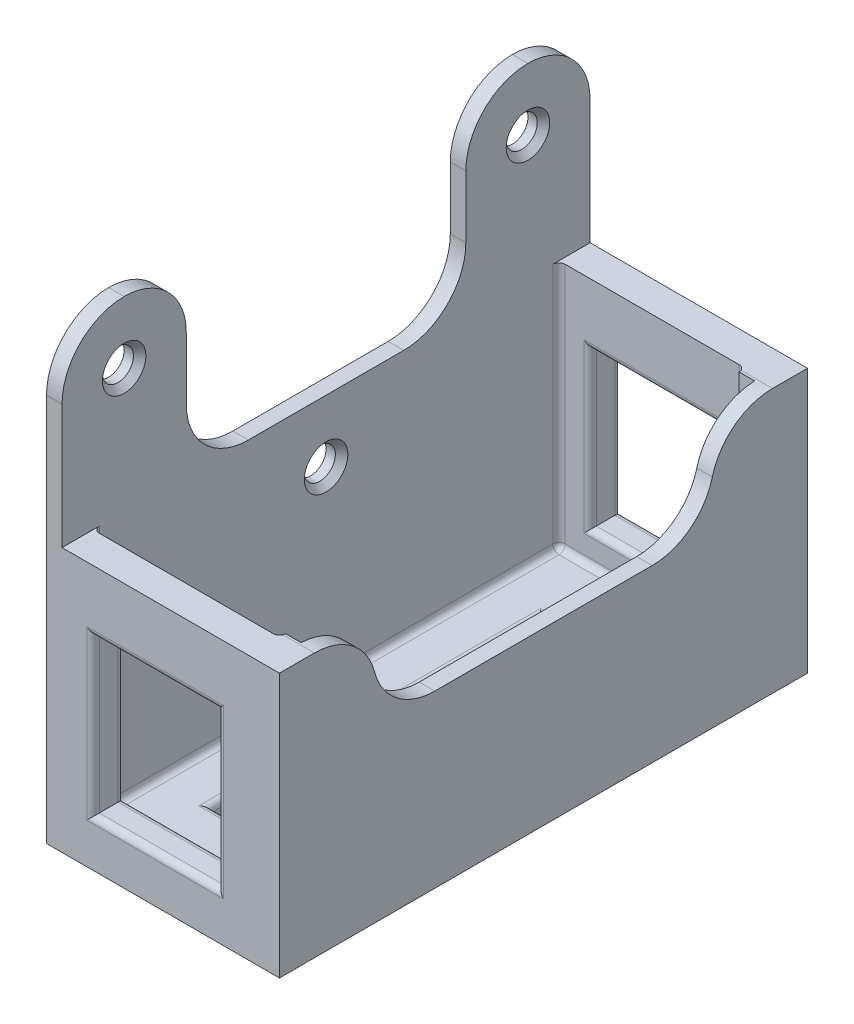
SolidWorks part; units mm, degrees
ref_plane "Front Plane" through (0, 0, 0) normal (0, 0, 1) x (1, 0, 0)
ref_plane "Top Plane" through (0, 0, 0) normal (0, 1, 0) x (1, 0, 0)
ref_plane "Right Plane" through (0, 0, 0) normal (1, 0, 0) x (0, 0, -1)
sketch "Sketch1" plane through (0, 0, 0) normal (0, 1, 0) x (1, 0, 0)
  line L1 (-31.1538, -30.9615) -> (8.8462, -30.9615)
  line L2 (-31.1538, -30.9615) -> (-31.1538, 54.0385)
  line L3 (-31.1538, 54.0385) -> (8.8462, 54.0385)
  line L4 (8.8462, -30.9615) -> (8.8462, 54.0385)
  dimension "D1" = 85
  dimension "D2" = 40
extrude "Boss-Extrude1" add sketch "Sketch1" along normal blind 75
sketch "Sketch3" plane through (0, 75, 0) normal (0, 1, 0) x (1, 0, 0)
  line L0 (-26.1538, -25.9615) -> (-26.1538, 49.0385)
  line L1 (-31.1538, -30.9615) -> (8.8462, -30.9615)
  line L2 (-31.1538, -30.9615) -> (-31.1538, 54.0385)
  line L3 (-31.1538, 54.0385) -> (8.8462, 54.0385)
  line L4 (8.8462, -30.9615) -> (8.8462, 54.0385)
  line L5 (-26.1538, 49.0385) -> (3.8462, 49.0385)
  line L6 (3.8462, -25.9615) -> (3.8462, 49.0385)
  line L7 (-26.1538, -25.9615) -> (3.8462, -25.9615)
  dimension "D1" = 5
extrude "Cut-Extrude2" cut sketch "Sketch3" against normal blind 70 flip side to cut
sketch "Sketch4" plane through (0, 75, 0) normal (0, 1, 0) x (1, 0, 0)
  line L0 (-31.1538, -30.9615) -> (8.8462, -30.9615) construction
  line L1 (-26.1538, -30.9615) -> (8.8462, -30.9615)
  line L2 (-26.1538, -30.9615) -> (-26.1538, 54.0385)
  line L3 (-26.1538, 54.0385) -> (8.8462, 54.0385)
  line L4 (8.8462, -30.9615) -> (8.8462, 54.0385)
extrude "Cut-Extrude3" cut sketch "Sketch4" against normal blind 30
fillet "Fillet1" radius 10 2 edges at (-28.6538, 75, -54.0385) (-28.6538, 75, 30.9615)
sketch "Sketch5" plane through (-26.1538, 0, 0) normal (1, 0, 0) x (0, 0, -1)
  circle A0 centre (-20.9615, 65) radius 2.5
  circle A1 centre (44.0385, 65) radius 2.5
extrude "Cut-Extrude4" cut sketch "Sketch5" against normal blind 30
chamfer "Chamfer1" distance 1 angle 45 2 edges at (-26.1538, 65, 18.4615) (-26.1538, 65, -46.5385)
sketch "Sketch6" plane through (8.8462, 0, 0) normal (1, 0, 0) x (0, 0, -1)
  line L0 (-30.9615, 45) -> (54.0385, 45) construction
  line L1 (-15.9615, 45) -> (39.0385, 45)
  line L2 (-15.9615, 45) -> (-15.9615, 40)
  line L3 (-5.9615, 30) -> (29.0385, 30)
  line L4 (39.0385, 45) -> (39.0385, 40)
  line L5 (-30.9615, 45) -> (-30.9615, 0) construction
  line L6 (54.0385, 45) -> (54.0385, 0) construction
  arc A0 (39.0385, 40) -> (29.0385, 30) centre (29.0385, 40) cw
  arc A1 (-5.9615, 30) -> (-15.9615, 40) centre (-5.9615, 40) cw
  point P14 (-15.9615, 30)
  dimension "D4" = 10
  dimension "D1" = 15
  dimension "D2" = 15
  dimension "D3" = 15
extrude "Cut-Extrude5" cut sketch "Sketch6" against normal blind 30
fillet "Fillet2" radius 1 8 edges at (3.8462, 25, -49.0385) (3.8462, 25, 25.9615) (3.8462, 5, -11.5385) (-11.1538, 5, -49.0385) (-26.1538, 25, -49.0385) (-26.1538, 25, 25.9615) (-11.1538, 5, 25.9615) (-26.1538, 5, -11.5385)
fillet "Fillet3" radius 10 2 edges at (6.3462, 45, 15.9615) (6.3462, 45, -39.0385)
sketch "Sketch7" plane through (0, 5, 0) normal (0, 1, 0) x (1, 0, 0)
  line L0 (2.8462, 48.0385) -> (-25.1538, 48.0385) construction
  line L1 (-18.1538, -14.9615) -> (-4.1538, -14.9615)
  line L2 (-18.1538, -14.9615) -> (-18.1538, 38.0385)
  line L3 (-18.1538, 38.0385) -> (-4.1538, 38.0385)
  line L4 (-4.1538, -14.9615) -> (-4.1538, 38.0385)
  line L5 (-25.1538, -24.9615) -> (2.8462, -24.9615) construction
  line L6 (-25.1538, 48.0385) -> (-25.1538, -24.9615) construction
  line L7 (2.8462, -24.9615) -> (2.8462, 48.0385) construction
  dimension "D1" = 10
  dimension "D2" = 10
  dimension "D3" = 7
  dimension "D4" = 7
extrude "Cut-Extrude6" cut sketch "Sketch7" against normal blind 30
fillet "Fillet4" radius 1 4 edges at (-11.1538, 5, 14.9615) (-4.1538, 5, -11.5385) (-11.1538, 5, -38.0385) (-18.1538, 5, -11.5385)
sketch "Sketch8" plane through (-26.1538, 0, 0) normal (1, 0, 0) x (0, 0, -1)
  line L0 (44.0385, 75) -> (-20.9615, 75) construction
  line L1 (-10.9615, 75) -> (34.0385, 75)
  line L2 (-10.9615, 75) -> (-10.9615, 55)
  line L3 (-0.9615, 45) -> (24.0385, 45)
  line L4 (34.0385, 75) -> (34.0385, 55)
  line L5 (-30.9615, 45) -> (-30.9615, 65) construction
  line L6 (54.0385, 45) -> (54.0385, 65) construction
  arc A0 (34.0385, 55) -> (24.0385, 45) centre (24.0385, 55) cw
  arc A1 (-0.9615, 45) -> (-10.9615, 55) centre (-0.9615, 55) cw
  dimension "D4" = 10
  dimension "D1" = 20
  dimension "D2" = 20
  dimension "D3" = 30
extrude "Cut-Extrude7" cut sketch "Sketch8" against normal blind 30
fillet "Fillet5" radius 10 2 edges at (-28.6538, 75, -34.0385) (-28.6538, 75, 10.9615)
sketch "Sketch9" plane through (-26.1538, 0, 0) normal (1, 0, 0) x (0, 0, -1)
  line L0 (-0.9615, 45) -> (24.0385, 45) construction
  circle A0 centre (11.5385, 35) radius 2.5
  dimension "D1" = 10
extrude "Cut-Extrude8" cut sketch "Sketch9" against normal blind 30
chamfer "Chamfer2" distance 1 angle 45 1 edges at (-26.1538, 35, -14.0385)
sketch "Sketch10" plane through (0, 0, 30.9615) normal (0, 0, 1) x (1, 0, 0)
  line L0 (-31.1538, 65) -> (-31.1538, 0) construction
  line L1 (-21.1538, 10) -> (-1.1538, 10)
  line L2 (-21.1538, 10) -> (-21.1538, 35)
  line L3 (-21.1538, 35) -> (-1.1538, 35)
  line L4 (-1.1538, 10) -> (-1.1538, 35)
  line L5 (8.8462, 45) -> (8.8462, 0) construction
  line L6 (-31.1538, 0) -> (8.8462, 0) construction
  line L7 (-26.1538, 45) -> (8.8462, 45) construction
  point P6 (8.8462, 22.5)
  dimension "D1" = 10
  dimension "D2" = 10
  dimension "D3" = 10
  dimension "D4" = 10
extrude "Cut-Extrude9" cut sketch "Sketch10" against normal blind 130
fillet "Fillet6" radius 1 8 edges at (-11.1538, 10, 25.9615) (-21.1538, 22.5, 25.9615) (-11.1538, 35, 25.9615) (-1.1538, 22.5, 25.9615) (-1.1538, 22.5, 30.9615) (-11.1538, 35, 30.9615) (-21.1538, 22.5, 30.9615) (-11.1538, 10, 30.9615)
fillet "Fillet7" radius 1 8 edges at (-1.1538, 22.5, -54.0385) (-1.1538, 22.5, -49.0385) (-11.1538, 35, -49.0385) (-11.1538, 35, -54.0385) (-21.1538, 22.5, -54.0385) (-21.1538, 22.5, -49.0385) (-11.1538, 10, -49.0385) (-11.1538, 10, -54.0385)
sketch "Sketch12" plane through (-31.1538, 0, 0) normal (-1, 0, 0) x (0, 0, 1)
  line L1 (-58.4389, 0) -> (40.7066, 0)
  line L2 (-58.4389, 0) -> (-58.4389, 91.5966)
  line L3 (-58.4389, 91.5966) -> (40.7066, 91.5966)
  line L4 (40.7066, 0) -> (40.7066, 91.5966)
extrude "Cut-Extrude11" cut sketch "Sketch12" against normal blind 2.5
sketch "Sketch13" plane through (0, 0, 0) normal (0, -1, 0) x (1, 0, 0)
  line L1 (-33.8468, 30.9615) -> (17.3815, 30.9615)
  line L2 (-33.8468, 30.9615) -> (-33.8468, -74.8318)
  line L3 (-33.8468, -74.8318) -> (17.3815, -74.8318)
  line L4 (17.3815, 30.9615) -> (17.3815, -74.8318)
extrude "Cut-Extrude12" cut sketch "Sketch13" against normal blind 2.5
sketch "Sketch14" plane through (3.8462, 0, 0) normal (-1, 0, 0) x (0, 0, 1)
  line L1 (24.9615, 6) -> (-48.0385, 6)
  line L2 (24.9615, 6) -> (24.9615, 76.0397)
  line L3 (24.9615, 76.0397) -> (-48.0385, 76.0397)
  line L4 (-48.0385, 6) -> (-48.0385, 76.0397)
extrude "Cut-Extrude13" cut sketch "Sketch14" against normal blind 2.5
